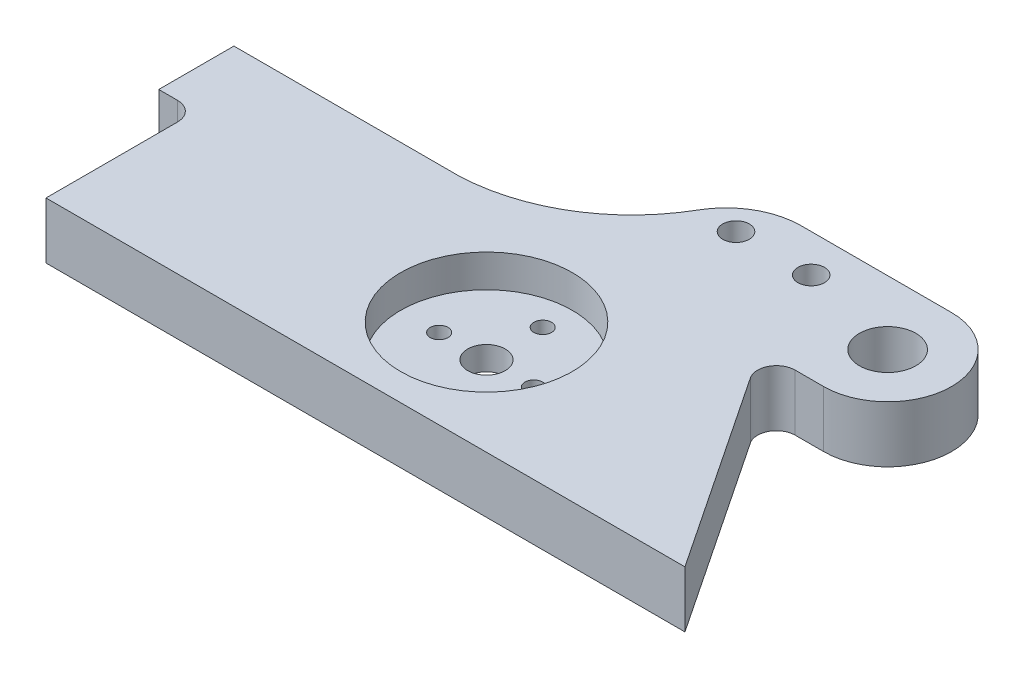
SolidWorks part; units mm, degrees
material "UHMW"
ref_plane "Front Plane" through (0, 0, 0) normal (0, 0, 1) x (1, 0, 0)
ref_plane "Top Plane" through (0, 0, 0) normal (0, 1, 0) x (1, 0, 0)
ref_plane "Right Plane" through (0, 0, 0) normal (1, 0, 0) x (0, 0, -1)
other "Bounding Box"
ref_plane "Default Plane" through (-8.9266, -12.7485, 0) normal (-0.1736, 0.9848, 0) x (0.9848, 0.1736, 0)
sketch "Sketch1" plane through (0, 0, 0) normal (0, 1, 0) x (1, 0, 0)
  line L0 (0, 0) -> (38.1, 0)
  line L1 (88.9, 0) -> (114.3, -38.1)
  line L2 (114.3, -38.1) -> (6.35, -38.1)
  line L3 (6.35, -38.1) -> (6.35, -12.7)
  line L4 (6.35, -12.7) -> (0, -12.7)
  line L5 (0, -12.7) -> (0, 0)
  line L6 (99.6289, 0) -> (88.9, 0)
  line L9 (99.6289, 21.632) -> (74.2289, 21.632)
  line L10 (61.7205, -19.05) -> (99.6289, 10.816) construction
  circle A0 centre (99.6289, 10.816) radius 4.7625
  arc A1 (99.6289, 21.632) -> (99.6289, 0) centre (99.6289, 10.816) cw
  arc A4 (74.2289, 21.632) -> (63.2185, 15.2614) centre (74.2289, 8.932) ccw
  arc A5 (63.2185, 15.2614) -> (38.1, 0) centre (36.7936, 30.452) cw
  circle A6 centre (69.5685, 15.2614) radius 2.2479
  circle A7 centre (82.2685, 15.2614) radius 2.2479
  circle B0 centre (69.7205, -19.05) radius 1.5
  circle B1 centre (61.7205, -28.55) radius 1.5
  circle B2 centre (53.7205, -19.05) radius 1.5
  circle B3 centre (61.7205, -9.55) radius 1.5
  circle B4 centre (61.7205, -19.05) radius 3.175
  dimension "D7" = 50.8
  dimension "D8" = 9.525
  dimension "D9" = 10.7289
  dimension "D6" = 10.816
  dimension "D10" = 30.48
  dimension "D16" = 12.7
  dimension "D19" = 4.4958
  dimension "D1" = 6.35
  dimension "D2" = 38.1
  dimension "D3" = 107.95
  dimension "D4" = 88.9
  dimension "D5" = 12.7
  dimension "D11" = 48.26
  dimension "D12" = 19.05
  dimension "D17" = 38.1
  dimension "D18" = 25.4
  dimension "D20" = 6.35
  dimension "D21" = 12.7
sketch_block_instance "Block1-1"
sketch_block "Block1" parameters "D1"=6.35
extrude "Boss-Extrude1" add sketch "Sketch1" along normal blind 9.525
fillet "Fillet1" radius 3.175 1 edges at (88.9, 4.7625, 0)
fillet "Fillet2" radius 3.175 1 edges at (6.35, 4.7625, 12.7)
sketch "Sketch2" plane through (0, 9.525, 0) normal (0, 1, 0) x (1, 0, 0)
  circle A0 centre (61.7205, -19.05) radius 14.5
  dimension "D1" = 29
extrude "Cut-Extrude1" cut sketch "Sketch2" against normal blind 5.525
